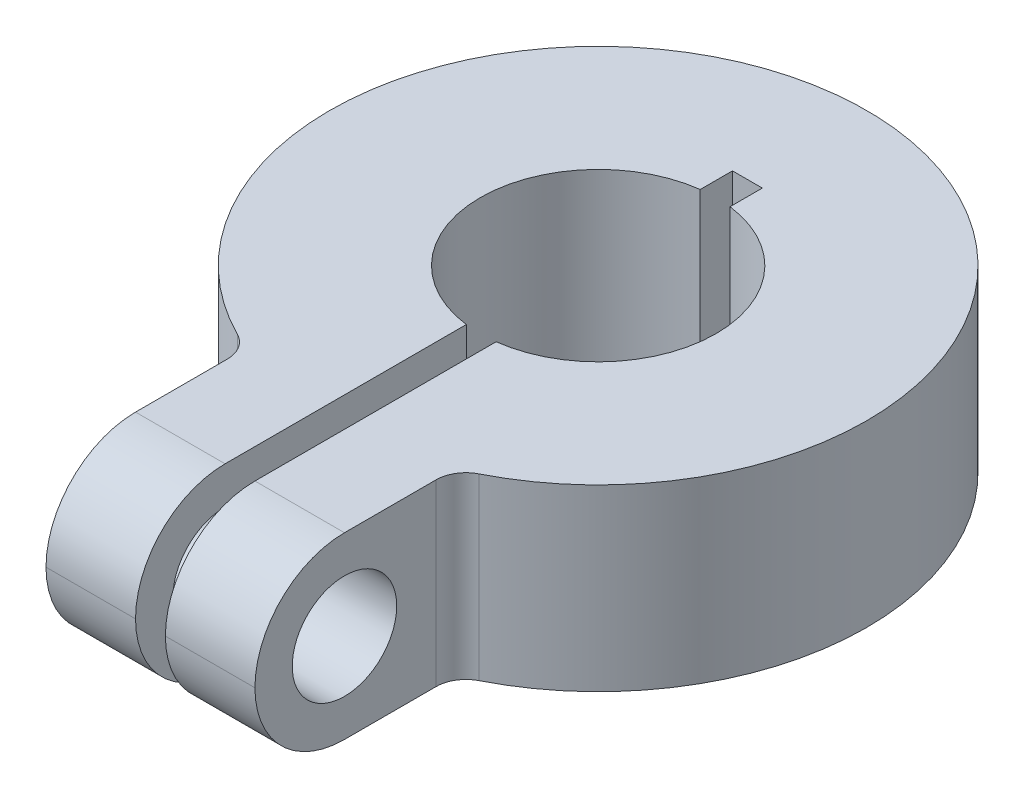
SolidWorks part; units mm, degrees
material "PLA"
ref_plane "Front Plane" through (0, 0, 0) normal (0, 0, 1) x (1, 0, 0)
ref_plane "Top Plane" through (0, 0, 0) normal (0, 1, 0) x (1, 0, 0)
ref_plane "Right Plane" through (0, 0, 0) normal (1, 0, 0) x (0, 0, -1)
sketch "Sketch1" plane through (0, 0, 0) normal (0, 1, 0) x (1, 0, 0)
  line L0 (0, 0) -> (0, -10.8089) construction
  line L2 (-3.5, -15) -> (3.5, -15)
  line L3 (-3.5, -15) -> (-3.5, -4)
  line L4 (-3.5, -4) -> (3.5, -4)
  line L5 (3.5, -15) -> (3.5, -4)
  line L6 (-3.5, -15) -> (3.5, -4) construction
  line L7 (-3.5, -4) -> (3.5, -15) construction
  circle A0 centre (0, 0) radius 3.95
  circle A1 centre (0, 0) radius 9
  point P5 (0, -9.5)
  dimension "D1" = 7.9
  dimension "D2" = 18
  dimension "D3" = 15
  dimension "D4" = 7
  dimension "D5" = 4
extrude "Boss-Extrude1" add sketch "Sketch1" along normal blind 6 contours L5 A1 L3 L4 A0 | L3 A1 L5 L4 | A1 L3 L2 L5 region at (0, 0, 11.8803) region at (-4.837, 0, -7.292) region at (0, 0, 6.3885)
sketch "Sketch2" plane through (0, 6, 0) normal (0, 1, 0) x (1, 0, 0)
  line L0 (0, 0) -> (0, -14.0673) construction
  line L1 (-3.5, -15) -> (3.5, -15) construction
  line L2 (-0.5, -15) -> (0.5, -15)
  line L3 (-0.5, -15) -> (-0.5, 5)
  line L4 (-0.5, 5) -> (0.5, 5)
  line L5 (0.5, -15) -> (0.5, 5)
  line L6 (-0.5, -15) -> (0.5, 5) construction
  line L7 (-0.5, 5) -> (0.5, -15) construction
  point P3 (0, -5)
  dimension "D1" = 1
  dimension "D2" = 20
extrude "Cut-Extrude1" cut sketch "Sketch2" against normal through all
fillet "Fillet1" radius 3 4 edges at (-2, 0, 15) (2, 0, 15) (-2, 6, 15) (2, 6, 15)
sketch "Sketch3" plane through (3.5, 0, 0) normal (1, 0, 0) x (0, 0, -1)
  circle A0 centre (-12, 3) radius 1.75
  arc A1 (-12, 6) -> (-15, 3) centre (-12, 3) ccw construction
  dimension "D1" = 3.5
extrude "Cut-Extrude2" cut sketch "Sketch3" against normal through all
fillet "Fillet2" radius 1 2 edges at (-3.5, 3, 8.2916) (3.5, 3, 8.2916)
